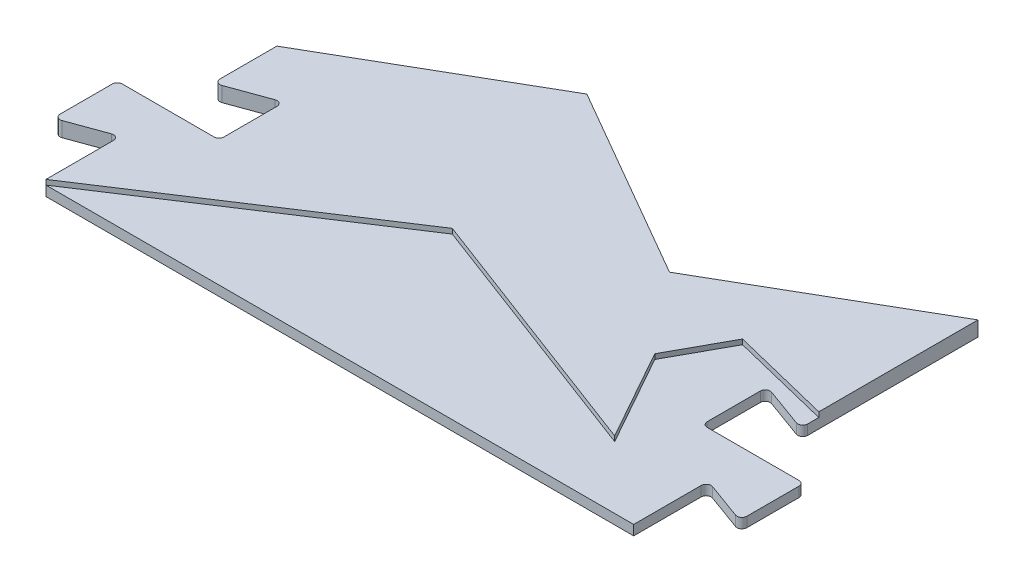
SolidWorks part; units mm, degrees
ref_plane "Přední rovina" through (0, 0, 0) normal (0, 0, 1) x (1, 0, 0)
ref_plane "Horní rovina" through (0, 0, 0) normal (0, 1, 0) x (1, 0, 0)
ref_plane "Pravá rovina" through (0, 0, 0) normal (1, 0, 0) x (0, 0, -1)
sketch "Skica1" plane through (0, 0, 0) normal (0, 1, 0) x (1, 0, 0)
  line L8 (-118.1438, 0) -> (-118.1438, 15)
  line L10 (-118.1438, 15) -> (-128.0938, 11.3785)
  line L11 (-128.0938, 11.3785) -> (-128.0938, 24.2785)
  line L12 (-107.6438, 24.2785) -> (-107.6438, 37.3785)
  line L13 (-107.6438, 37.3785) -> (-118.1432, 33.557)
  line L17 (-118.1432, 33.557) -> (-118.1432, 46.41)
  line L18 (-118.1432, 46.41) -> (-78.6351, 69.22)
  line L19 (-78.6351, 69.22) -> (-39.3176, 46.52)
  line L20 (-118.1438, 15) -> (-118.1438, 56.5658) construction
  line L21 (-107.6438, 24.2785) -> (-128.0938, 24.2785)
  line L22 (-68.7793, 32.3134) -> (-118.1438, 0)
  line L23 (-68.7793, 32.3134) -> (-16.3273, 12.5112)
  line L24 (-16.3273, 12.5112) -> (-26.5931, 30.831)
  line L25 (-26.5931, 30.831) -> (-20.3432, 42.23)
  line L26 (-39.3176, 46.52) -> (0, 69.22)
  line L28 (-118.1438, 0) -> (0, 0)
  line L29 (-20.3432, 42.23) -> (0, 37.22)
  line L30 (0, 0) -> (0, 15)
  line L33 (0, 69.22) -> (0, 0) construction
  line L34 (-10.5, 24.2783) -> (9.9505, 24.2783)
  line L39 (0, 69.22) -> (0, 33.5566)
  line L40 (0, 15) -> (9.9505, 11.3783)
  line L41 (9.9505, 24.2783) -> (9.9505, 11.3783)
  line L42 (0, 33.5566) -> (-10.5, 37.3783)
  line L43 (-10.5, 37.3783) -> (-10.5, 24.2783)
  point P27 (-0.2747, 24.2783)
  dimension "D1" = 45.4
  dimension "D2" = 45.62
  dimension "D3" = 120
  dimension "D4" = 70
  dimension "D5" = 12.9
  dimension "D6" = 13.1
  dimension "D7" = 70
  dimension "D8" = 10.5
  dimension "D9" = 15
  dimension "D10" = 122
  dimension "D11" = 13
  dimension "D12" = 21
  dimension "D13" = 56.0655
  dimension "D14" = 120
  dimension "D15" = 59
  dimension "D16" = 45.4
  dimension "D17" = 120
  dimension "D18" = 118.1438
  dimension "D19" = 104.9
  dimension "D20" = 32.3134
  dimension "D21" = 70
  dimension "D22" = 13.1
  dimension "D23" = 70
  dimension "D24" = 10.5
  dimension "D25" = 15
  dimension "D26" = 12.5112
  dimension "D27" = 69.22
  dimension "D28" = 32
  dimension "D29" = 12.9
  dimension "D30" = 69.22
  dimension "D31" = 9.95
extrude "Přidat vysunutím1" add sketch "Skica1" along normal blind 3 contours L20 L23 L24 L25 L29 L39 L26 L19 L18 L17 L13 L12 L21 | L10 L20 L21 L11 region at (-66.762, 0, -39.2146)
extrude "Přidat vysunutím2" add sketch "Skica1<5>" along normal blind 2 contours L43 L42 L39 L29 L25 L24 L23 L8 L28 L30 L40 L41 L34 region at (-46.7963, 0, -13.9892)
sketch "Skica1<5>" plane through (0, 0, 0) normal (0, 1, 0) x (1, 0, 0) same geometry as "Skica1"
fillet "Zaoblit4" radius 1 12 edges at (0, 1, -33.5566) (-10.5, 1, -24.2783) (-10.5, 1, -37.3783) (0, 1, -15) (9.9505, 1, -11.3783) (9.9505, 1, -24.2783) (-128.0938, 1.5, -11.3785) (-128.0938, 1.5, -24.2785) (-107.6438, 1.5, -24.2785) (-107.6438, 1.5, -37.3785) (-118.1432, 1.5, -33.557) (-118.1438, 1.5, -15)
